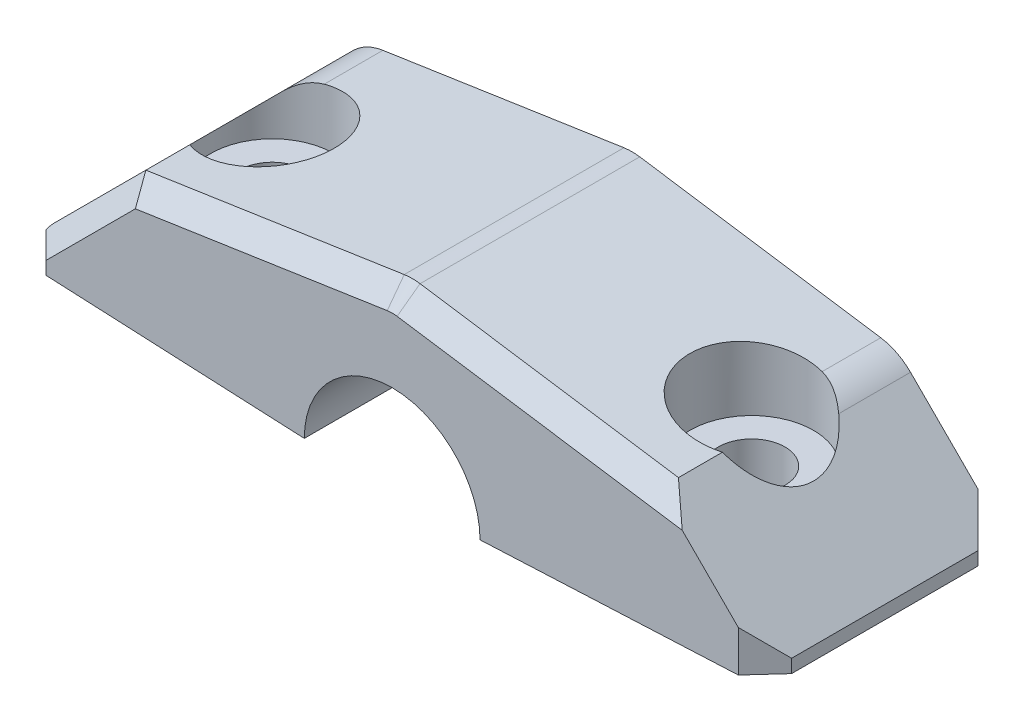
SolidWorks part; units mm, degrees
ref_plane "Front Plane" through (0, 0, 0) normal (0, 0, 1) x (1, 0, 0)
ref_plane "Top Plane" through (0, 0, 0) normal (0, 1, 0) x (1, 0, 0)
ref_plane "Right Plane" through (0, 0, 0) normal (1, 0, 0) x (0, 0, -1)
sketch "Sketch1" plane through (0, 0, 0) normal (0, 0, 1) x (1, 0, 0)
  line L1 (-14, 0.5) -> (-14, 6.5)
  line L2 (-14, 6.5) -> (14, 6.5)
  line L3 (0, 6.5) -> (0, 3.3) construction
  line L4 (14, 0.5) -> (14, 6.5)
  line L6 (-3.3, 0) -> (-14, 0.5)
  line L7 (3.3, 0) -> (14, 0.5)
  arc A0 (3.3, 0) -> (-3.3, 0) centre (0, 0) ccw
  dimension "D1" = 6.6
  dimension "D2" = 28
  dimension "D3" = 6.5
  dimension "D4" = 6
extrude "Boss-Extrude1" add sketch "Sketch1" along normal blind 9
sketch "Sketch2" plane through (0, 0, 9) normal (0, 0, 1) x (1, 0, 0)
  line L0 (0, 6.5) -> (-10, 5)
  line L1 (14, 6.5) -> (-14, 6.5) construction
  line L2 (-10, 5) -> (-14, 1)
  line L3 (-14, 6.5) -> (-14, 0.5) construction
  line L4 (-14, 1) -> (-14, 6.5)
  line L5 (-14, 6.5) -> (14, 6.5)
  line L6 (0, 8.1862) -> (0, -3.9101) construction
  line L7 (14, 1) -> (14, 6.5)
  line L8 (10, 5) -> (14, 1)
  line L9 (0, 6.5) -> (10, 5)
  line M8 (14, 0.5) -> (14, 6.5)
  line M9 (14, 6.5) -> (-14, 6.5)
  line M10 (-14, 6.5) -> (-14, 0.5)
  dimension "D1" = 5
  dimension "D2" = 20
  dimension "D3" = 5.5
extrude "Cut-Extrude1" cut sketch "Sketch2" against normal through all both and the other way through all contours L2 L0 M9 M10 | L9 L8 M9 M8
chamfer "Chamfer1" distance 1 angle 45 4 edges at (-14, 0.75, 0) (14, 0.75, 0) (14, 0.75, 9) (-14, 0.75, 9)
sketch "Sketch4" plane through (0, 0, 0) normal (0, 1, 0) x (-1, 0, 0)
  line L0 (0, 9) -> (0, 0) construction
  line L1 (-9, 4.5) -> (9, 4.5) construction
  line L2 (3.3, 9) -> (-3.3, 9) construction
  line L4 (-3.3, 0) -> (3.3, 0) construction
  circle A0 centre (-9, 4.5) radius 1.25
  circle A1 centre (9, 4.5) radius 1.25
  point P8 (0, 4.5)
  point P17 (0, 4.5)
  dimension "D2" = 2.5
  dimension "D1" = 18
extrude "Cut-Extrude2" cut sketch "Sketch4" along normal through all
sketch "Sketch5" plane through (0, 0, 0) normal (0, 1, 0) x (1, 0, 0)
  circle A0 centre (9, -4.5) radius 2.325
  circle A1 centre (-9, -4.5) radius 2.325
  dimension "D1" = 4.65
extrude "Cut-Extrude3" cut sketch "Sketch5" along normal blind 10 from offset 3
fillet "Fillet2" radius 2 4 edges at (10, 5, 1.2005) (-10, 5, 1.2005) (-14, 1, 4.5)
chamfer "Chamfer3" distance 0.75 angle 45 4 edges at (-11.5, 3.5, 9) (0, 6.4776, 9)
